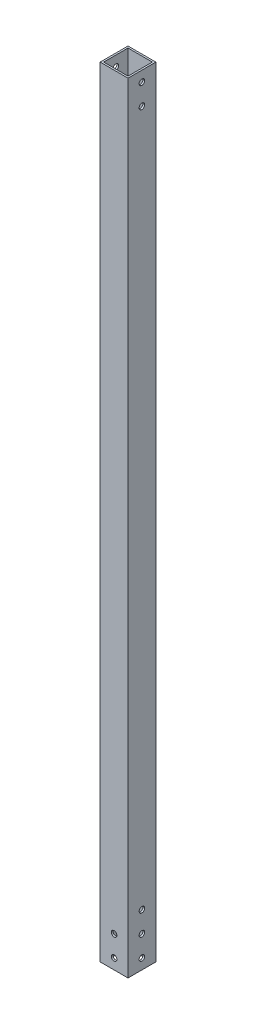
SolidWorks part; units mm, degrees
material "6061-T6 (SS)"
ref_plane "Front Plane" through (0, 0, 0) normal (0, 0, 1) x (1, 0, 0)
ref_plane "Top Plane" through (0, 0, 0) normal (0, 1, 0) x (1, 0, 0)
ref_plane "Right Plane" through (0, 0, 0) normal (1, 0, 0) x (0, 0, -1)
sketch "Sketch1" plane through (0, 0, 0) normal (0, 1, 0) x (1, 0, 0)
  line L0 (11.1125, 11.1125) -> (-11.1125, 11.1125)
  line L1 (12.7, -12.7) -> (-12.7, -12.7)
  line L2 (12.7, -12.7) -> (12.7, 12.7)
  line L3 (12.7, 12.7) -> (-12.7, 12.7)
  line L4 (-12.7, -12.7) -> (-12.7, 12.7)
  line L5 (12.7, -12.7) -> (-12.7, 12.7) construction
  line L6 (12.7, 12.7) -> (-12.7, -12.7) construction
  line L7 (-11.1125, -11.1125) -> (-11.1125, 11.1125)
  line L8 (11.1125, -11.1125) -> (-11.1125, -11.1125)
  line L9 (11.1125, -11.1125) -> (11.1125, 11.1125)
  point P0 (0, 0)
  dimension "D1" = 25.4
  dimension "D2" = 1.5875
extrude "Boss-Extrude1" add sketch "Sketch1" along normal blind 711.2
sketch "Sketch2" plane through (0, 0, 12.7) normal (0, 0, 1) x (1, 0, 0)
  line L0 (-12.7, 0) -> (12.7, 0) construction
  circle A0 centre (0, 9.525) radius 2.5527
  circle A1 centre (0, 28.575) radius 2.5527
  point P7 (0, 0)
  dimension "D1" = 9.525
  dimension "D2" = 19.05
  dimension "D3" = 5.1054
extrude "Cut-Extrude1" cut sketch "Sketch2" against normal through all
sketch "Sketch3" plane through (12.7, 0, 0) normal (1, 0, 0) x (0, 0, -1)
  line L0 (-12.7, 0) -> (12.7, 0) construction
  line L1 (-12.7, 711.2) -> (12.7, 711.2) construction
  circle A0 centre (0, 9.525) radius 2.5527
  circle A1 centre (0, 28.575) radius 2.5527
  circle A2 centre (0, 47.625) radius 2.5527
  circle A3 centre (0, 701.675) radius 2.5527
  circle A4 centre (0, 682.625) radius 2.5527
  point P9 (0, 0)
  dimension "D1" = 9.525
  dimension "D2" = 19.05
  dimension "D3" = 19.05
  dimension "D4" = 5.1054
  dimension "D5" = 9.525
  dimension "D6" = 19.05
extrude "Cut-Extrude2" cut sketch "Sketch3" against normal through all
